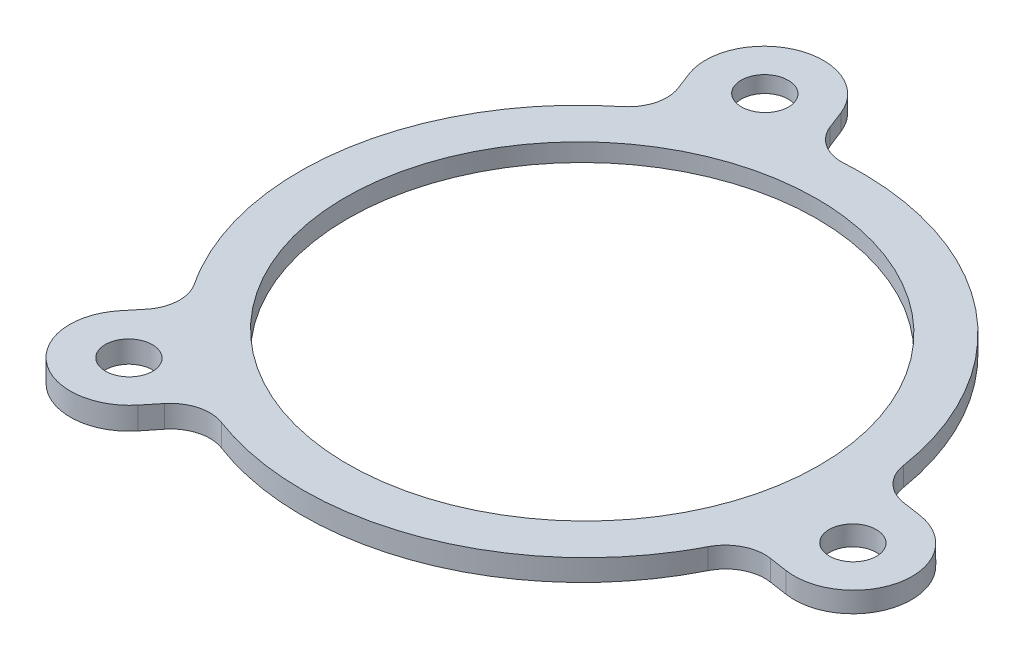
SolidWorks part; units mm, degrees
material "5454-O"
ref_plane "Front Plane" through (0, 0, 0) normal (0, 0, 1) x (1, 0, 0)
ref_plane "Top Plane" through (0, 0, 0) normal (0, 1, 0) x (1, 0, 0)
ref_plane "Right Plane" through (0, 0, 0) normal (1, 0, 0) x (0, 0, -1)
sketch "Sketch1" plane through (0, 0, 0) normal (0, 0, 1) x (1, 0, 0)
  line L0 (-3.7459, 1) -> (5.6477, 1) construction
  dimension "D1" = 1
ref_plane "Plane1" through (0, 0.9999, -0.0099) normal (0, 1, -0.0099) x (1, 0, 0)
sketch "Sketch2" plane through (0, 0, 0) normal (0, 1, 0) x (1, 0, 0)
  line L0 (0, 0) -> (-6.0205, 15.3624) construction
  line L1 (0, 0) -> (-10.294, -12.8951) construction
  line L2 (0, 0) -> (16.3145, -2.4673) construction
  line L3 (-6.0205, 15.3624) -> (-3.2273, 16.4571) construction
  line L4 (-6.0205, 15.3624) -> (-8.8136, 14.2678) construction
  line L5 (-3.2273, 16.4571) -> (-2.3151, 14.1294) construction
  line L6 (-8.8136, 14.2678) -> (-7.9014, 11.9402) construction
  line L7 (16.3145, -2.4673) -> (16.7631, 0.4989) construction
  line L8 (16.3145, -2.4673) -> (15.8659, -5.4336) construction
  line L9 (16.7631, 0.4989) -> (14.2912, 0.8728) construction
  line L10 (15.8659, -5.4336) -> (13.394, -5.0598) construction
  line L11 (-10.294, -12.8951) -> (-7.9495, -14.7667) construction
  line L12 (-10.294, -12.8951) -> (-12.6386, -11.0234) construction
  line L13 (-12.6386, -11.0234) -> (-11.0789, -9.0696) construction
  line L14 (-7.9495, -14.7667) -> (-6.3898, -12.8129) construction
  line L15 (-8.8136, 14.2678) -> (-8.4608, 13.3674)
  line L16 (-3.2273, 16.4571) -> (-2.8744, 15.5566)
  line L17 (16.7631, 0.4989) -> (15.8069, 0.6436)
  line L18 (15.8659, -5.4336) -> (14.9097, -5.289)
  line L19 (-7.9495, -14.7667) -> (-7.3461, -14.0109)
  line L20 (-12.6386, -11.0234) -> (-12.0352, -10.2676)
  arc A0 (-8.8136, 14.2678) -> (-3.2273, 16.4571) centre (-6.0205, 15.3624) cw
  arc A1 (16.7631, 0.4989) -> (15.8659, -5.4336) centre (16.3145, -2.4673) cw
  arc A2 (-7.9495, -14.7667) -> (-12.6386, -11.0234) centre (-10.294, -12.8951) cw
  arc A3 (-0.8882, 14.2902) -> (14.1319, 2.2998) centre (0, 0) cw
  arc A4 (12.8198, -6.3759) -> (-5.0743, -13.3885) centre (0, 0) cw
  arc A5 (-11.9316, -7.9144) -> (-9.0576, 11.0887) centre (0, 0) cw
  arc A6 (-11.9316, -7.9144) -> (-12.0352, -10.2676) centre (-13.5983, -9.0199) cw
  arc A7 (12.8198, -6.3759) -> (14.9097, -5.289) centre (14.6106, -7.2665) cw
  arc A8 (-0.8882, 14.2902) -> (-2.8744, 15.5566) centre (-1.0123, 16.2864) cw
  arc A9 (-7.3461, -14.0109) -> (-5.0743, -13.3885) centre (-5.7831, -15.2587) cw
  arc A10 (15.8069, 0.6436) -> (14.1319, 2.2998) centre (16.1059, 2.6211) cw
  arc A11 (-9.0576, 11.0887) -> (-8.4608, 13.3674) centre (-10.3229, 12.6376) ccw
  circle A12 centre (0, 0) radius 12
  circle A13 centre (-6.0205, 15.3624) radius 1.2
  circle A14 centre (16.3145, -2.4673) radius 1.2
  circle A15 centre (-10.294, -12.8951) radius 1.2
  dimension "D1" = 2
  dimension "D2" = 2
extrude "Boss-Extrude1" add sketch "Sketch2" along normal up to surface (0.8581 mm away) up to plane "Plane1"
sketch3d "3DSketch1"
  point P0 (20.3145, 1.4981, 16.8951)
